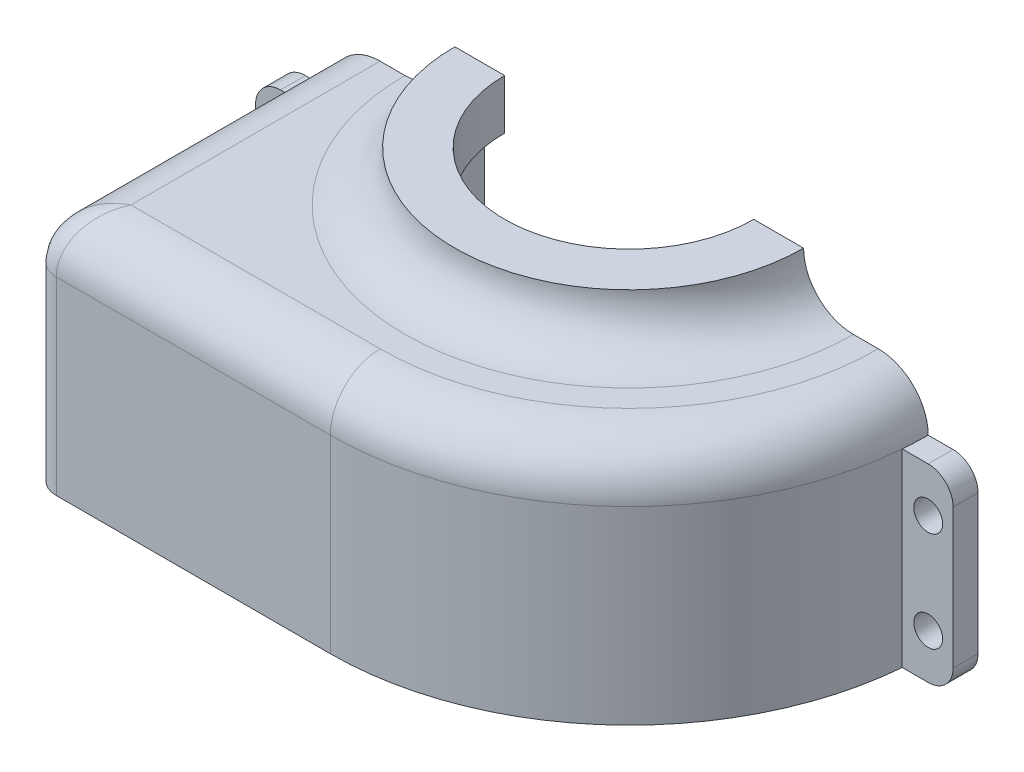
SolidWorks part; units mm, degrees
ref_plane "Front Plane" through (0, 0, 0) normal (0, 0, 1) x (1, 0, 0)
ref_plane "Top Plane" through (0, 0, 0) normal (0, 1, 0) x (1, 0, 0)
ref_plane "Right Plane" through (0, 0, 0) normal (1, 0, 0) x (0, 0, -1)
sketch "Sketch2" plane through (0, 0, 0) normal (0, 1, 0) x (1, 0, 0)
  line L5 (31.7809, -26.6264) -> (-31.7809, 26.6264) construction
  line L6 (31.7809, 26.6264) -> (-31.7809, -26.6264) construction
  line L7 (0, 0) -> (-60, 0)
  line L8 (0, 0) -> (0, -60)
  line L9 (0, -60) -> (-55, -60)
  line L10 (-60, 0) -> (-60, -55)
  circle A0 centre (0, 0) radius 20
  circle A1 centre (0, 0) radius 60
  arc A2 (-60, -55) -> (-55, -60) centre (-55, -55) ccw
  point P0 (0, 0)
  dimension "D1" = 120
  dimension "D2" = 5
extrude "Boss-Extrude2" add sketch "Sketch2" against normal blind 5 contours L10 A2 L9 A1 | L7 A1 L8 A0 | L8 A1 L7 A0 region at (-27.5869, 0, 27.5869) region at (-40, 0, -1.6971) region at (-46.512, 0, 46.512)
sketch "Sketch3" plane through (0, 0, 0) normal (0, 1, 0) x (1, 0, 0)
  line L8 (-55, 0) -> (-55, -52)
  line L9 (-52, -55) -> (0, -55)
  line L14 (-60, 0) -> (-60, -55)
  line L15 (-55, -60) -> (0, -60)
  arc A10 (0, -55) -> (-55, 0) centre (0, 0) ccw
  arc A11 (-55, -52) -> (-52, -55) centre (-52, -52) ccw
  arc A15 (0, -60) -> (-60, 0) centre (0, 0) ccw
  arc A16 (-60, -55) -> (-55, -60) centre (-55, -55) ccw
  dimension "D3" = 3
extrude "Boss-Extrude3" add sketch "Sketch3" along normal blind 18
sketch "Sketch4" plane through (0, 18, 0) normal (0, 1, 0) x (1, 0, 0)
  line L4 (-60, 0) -> (-60, -55)
  line L5 (-55, -60) -> (0, -60)
  line L6 (-60, 0) -> (-60, -55)
  line L7 (-55, -60) -> (0, -60)
  circle A1 centre (0, 0) radius 29
  arc A6 (0, -60) -> (-60, 0) centre (0, 0) ccw
  arc A7 (-60, -55) -> (-55, -60) centre (-55, -55) ccw
  arc A8 (0, -60) -> (-60, 0) centre (0, 0) ccw
  arc A9 (-60, -55) -> (-55, -60) centre (-55, -55) ccw
  dimension "D1" = 58
  dimension "D2" = 0
extrude "Boss-Extrude4" add sketch "Sketch4" along normal blind 25
sketch "Sketch5" plane through (0, 43, 0) normal (0, 1, 0) x (1, 0, 0)
  circle A0 centre (0, 0) radius 25
  circle A1 centre (0, 0) radius 35
  dimension "D1" = 50
  dimension "D2" = 10
extrude "Boss-Extrude5" add sketch "Sketch5" along normal blind 10
fillet "Fillet4" radius 10 5 edges at (-27.5, 43, 60) (-58.5355, 43, 58.5355) (-60, 43, 27.5) (42.4264, 43, -42.4264) (0, 43, 35)
sketch "Sketch6" plane through (0, 0, 0) normal (0, 0, 1) x (1, 0, 0)
  line L1 (-60, 33) -> (-70, 33)
  line L2 (-60, 33) -> (-60, -5)
  line L3 (-60, -5) -> (-70, -5)
  line L4 (-70, 33) -> (-70, -5)
  line L10 (-54.2212, 3.0202) -> (-70, 33) construction
  line L11 (-50.7001, 31.6699) -> (-70, -5) construction
  point P7 (-60, 14)
  dimension "D1" = 0
  dimension "D2" = 10
  dimension "D3" = 0
extrude "Boss-Extrude7" add sketch "Sketch6" along normal mid plane 10 separate body
sketch "Sketch7" plane through (-70, 0, 0) normal (-1, 0, 0) x (0, 0, 1)
  line L1 (5, 33) -> (-5, 33)
  line L2 (5, 33) -> (5, -5)
  line L3 (5, -5) -> (-5, -5)
  line L4 (-5, 33) -> (-5, -5)
extrude "Boss-Extrude8" add sketch "Sketch7" against normal up to surface (10.2087 mm away) up to face at (6.2132, 14, -6.2132)
sketch "Sketch8" plane through (0, 0, 5) normal (0, 0, 1) x (1, 0, 0)
  line L0 (-65, 4) -> (-65, 24)
  line L1 (-60, 33) -> (-70, 33) construction
  line L2 (-70, -5) -> (-70, 33) construction
  point P3 (-65, 14)
  point P5 (-65, 33)
  point P8 (-70, 14)
  dimension "D1" = 0
  dimension "D2" = 0
  dimension "D3" = 20
hole_wizard "M5 Clearance Hole1" positions "Sketch9" profile "Sketch10" hole size "M5" standard "ANSI Metric" end condition through all
sketch "Sketch9" plane through (0, 0, 5) normal (0, 0, 1) x (1, 0, 0)
  point P0 (-65, 4)
  point P3 (-65, 24)
sketch "Sketch10" plane through (-65, 4, 5) normal (1, 0, 0) x (0, -1, 0)
  line L0 (0, 0) -> (0, 65)
  line L1 (0, 65) -> (2.9, 65)
  line L2 (2.9, 65) -> (2.9, 0)
  line L5 (2.9, 0) -> (0, 0)
  line L11 (0, -6.35) -> (0, 107.95) construction
  dimension "Thru Hole Dia." = 5.8
  dimension "Thru Hole Depth" = 65
fillet "Fillet3" radius 5 2 edges at (-70, -5, 0) (-70, 33, 0)
mirror "Mirror1" about plane through (0, 0, 0) normal (1, 0, 0) of "M5 Clearance Hole1", "Fillet3", "Boss-Extrude8"
split "Split1" trim tools "Front Plane" bodies to split 113 110 resulting bodies 111 112
delete or keep bodies "Body-Delete/Keep 1" type delete bodies bodies 112
